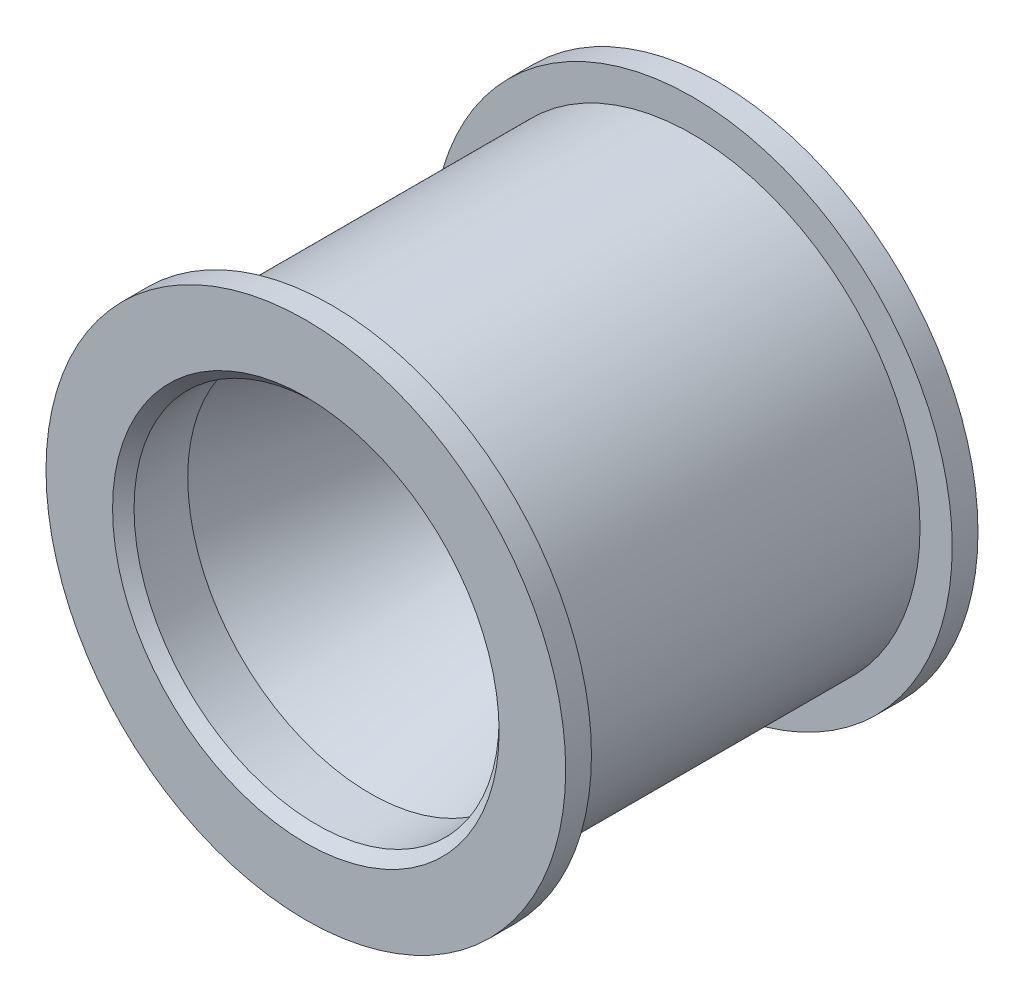
SolidWorks part; units mm, degrees
ref_plane "Ebene vorne" through (0, 0, 0) normal (0, 0, 1) x (1, 0, 0)
ref_plane "Ebene oben" through (0, 0, 0) normal (0, 1, 0) x (1, 0, 0)
ref_plane "Ebene rechts" through (0, 0, 0) normal (1, 0, 0) x (0, 0, -1)
sketch "Skizze1" plane through (0, 0, 0) normal (0, 0, 1) x (1, 0, 0)
  circle A0 centre (0, 0) radius 10.6
  dimension "D1" = 21.2
extrude "Laufrad" add sketch "Skizze1" along normal blind 8.4 and the other way blind 8.4
sketch "Skizze2" plane through (0, 0, 8.4) normal (0, 0, 1) x (1, 0, 0)
  circle A0 centre (0, 0) radius 12.1
  circle A1 centre (0, 0) radius 10.6 construction
  dimension "D1" = 1.5
extrude "Kettenführung" add sketch "Skizze2" along normal blind 1.2
mirror "Spiegeln Kettenführung" about plane through (0, 0, 0) normal (0, 0, 1) of "Kettenführung"
sketch "Skizze4" plane through (0, 0, -9.6) normal (0, 0, -1) x (-1, 0, 0)
  circle A0 centre (0, 0) radius 1.65
  dimension "D1" = 3.3
extrude "SchraubenBohrung M3" cut sketch "Skizze4" against normal through all
sketch "Skizze3" plane through (0, 0, -9.6) normal (0, 0, -1) x (-1, 0, 0)
  circle A0 centre (0, 0) radius 4.1
  dimension "D1" = 8.2
extrude "Kugellagersitz" cut sketch "Skizze3" against normal blind 4
sketch "Skizze5" plane through (0, 0, 0) normal (1, 0, 0) x (0, 0, -1)
  line L0 (-9.6, 0) -> (-9.6, 8.5)
  line L1 (-9.6, 8.5) -> (-6.6, 8.5)
  line L2 (-6.6, 8.5) -> (2.6, 6)
  line L3 (2.6, 6) -> (2.6, 0)
  line L4 (9.6, -4.1) -> (9.6, 4.1) construction
  line L5 (-9.6, 0) -> (5.6, 0) construction
  line L6 (-9.6, 0) -> (2.6, 0)
  line L7 (-9.6, 12.1) -> (-9.6, -12.1) construction
  dimension "D1" = 7
  dimension "D2" = 3
  dimension "D3" = 8.5
  dimension "D4" = 6
revolve "Schnitt-Rotation3" cut sketch "Skizze5" angle 360 about axis through (0, 0, -8.4) along (0, 0, 1)
chamfer "Fase1" distance 0.5 angle 45 5 edges at (-1.65, 0, -2.6) (-1.65, 0, -5.6) (-4.1, 0, -9.6) (-8.5, 0, 9.6) (-6, 0, -2.6) first distance on face at (-6, 0, -2.6) first distance on face at (-1.65, 0, -2.6) first distance on face at (-4.1, 0, -9.6) first distance on face at (-8.5, 0, 9.6)
sketch "Skizze6" [suppressed] plane through (0, 0, 0) normal (0, 0, 1) x (1, 0, 0)
  line L0 (0, 0) -> (0, 10.3) construction
  line L1 (0, 10.3) -> (0, 11.1) construction
  line L2 (0.55, 11.1) -> (-0.55, 11.1)
  line L3 (-0.55, 11.1) -> (-0.95, 10.5424)
  line L4 (-0.95, 10.5424) -> (-0.95, 9.5529)
  line L5 (0.95, 10.5424) -> (0.95, 9.5529)
  line L6 (0.55, 11.1) -> (0.95, 10.5424)
  line L7 (-0.95, 9.5529) -> (0.95, 9.5529)
  circle A1 centre (0, 0) radius 9.6 construction
  dimension "D1" = 0.8
  dimension "D2" = 10.3
  dimension "D3" = 1.9
  dimension "D4" = 1.1
extrude "Zahn" [suppressed] add sketch "Skizze6" along normal blind 2.8 and the other way blind 2.8
fillet "Verrundung1" [suppressed] radius 0.3
pattern_circular "Kreismuster1" [suppressed] count 7 over 360 of bodies 107
sketch "Skizze7" [suppressed] plane through (0, 0, -2.6) normal (0, 0, 1) x (1, 0, 0)
  circle A0 centre (0, 0) radius 8
  circle A1 centre (0, 0) radius 1.25
  dimension "D1" = 2.5
  dimension "D2" = 16
extrude "Aufsatz-Linear austragen1" [suppressed] add sketch "Skizze7" against normal offset from surface (9 mm away) 2 offset beyond the face yes
sketch "Skizze8" [suppressed] plane through (0, 0, -11.6) normal (0, 0, -1) x (-1, 0, 0)
  line L0 (0, 8) -> (0, 0) construction
  line L1 (0, 0) -> (8, 0) construction
  line L2 (-2.1, 3.4044) -> (-2.1, 13)
  line L3 (-2.1, 13) -> (2.1, 13)
  line L4 (2.1, 3.4044) -> (2.1, 13)
  line L5 (2.1, -3.4044) -> (2.1, -13)
  line L6 (-2.1, -13) -> (2.1, -13)
  line L7 (-2.1, -3.4044) -> (-2.1, -13)
  line L8 (2.1, 3.4044) -> (16, 2.5)
  line L9 (16, 2.5) -> (16, -2.5)
  line L10 (2.1, -3.4044) -> (16, -2.5)
  line L11 (-2.1, -3.4044) -> (-16, -2.5)
  line L12 (-16, 2.5) -> (-16, -2.5)
  line L13 (-2.1, 3.4044) -> (-16, 2.5)
  circle A0 centre (0, 0) radius 8 construction
  circle A1 centre (0, 0) radius 8 construction
  point P15 (0, 13)
  point P21 (16, 0)
  dimension "D1" = 8
  dimension "D2" = 4.2
  dimension "D3" = 26
  dimension "D4" = 5
  dimension "D5" = 32
extrude "Schnitt-Linear austragen1" [suppressed] cut sketch "Skizze8" against normal blind 1.4
sketch "Skizze9" [suppressed] plane through (0, 0, -2.6) normal (0, 0, 1) x (1, 0, 0)
  circle A0 centre (0, 0) radius 2.5
  dimension "D1" = 5
extrude "Schnitt-Linear austragen2" [suppressed] cut sketch "Skizze9" against normal offset from surface (5.6 mm away) 2
chamfer "Fase2" [suppressed] distance 0.5 angle 45
chamfer "Fase3" [suppressed] distance 2 angle 45
chamfer "Fase4" [suppressed] distance 0.3 angle 45
